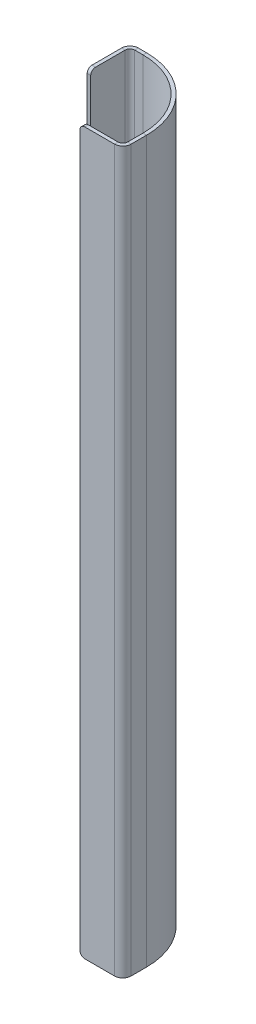
SolidWorks part; units mm, degrees
note: The reader was unsure of these and kept them because the rebuilt part matched: flange length of "Ребро-кромка4", "Ребро-кромка9", "Ребро-кромка10".
ref_plane "Спереди" through (0, 0, 0) normal (0, 0, 1) x (1, 0, 0)
ref_plane "Сверху" through (0, 0, 0) normal (0, 1, 0) x (1, 0, 0)
ref_plane "Справа" through (0, 0, 0) normal (1, 0, 0) x (0, 0, -1)
sketch "Эскиз8" plane through (0, 0, 0) normal (0, 0, 1) x (1, 0, 0)
  line L1 (0, 0) -> (3.5, 0)
  line L2 (0, 0) -> (0, 303)
  line L3 (0, 303) -> (3.5, 303)
  line L4 (3.5, 0) -> (3.5, 303)
  dimension "D1" = 303
  dimension "D2" = 3.5
base flange "Базовая кромка3" sketch "Эскиз8" thickness 1.5 reverse thickness direction no parameters "D1"=2
edge flange "Ребро-кромка4" sketch "Эскиз34" flange angle 90 flange length 35 flange position bend outside bend radius 28.5 thickness 1.5 relief rectangular parameters "D6"=10
sketch "Эскиз34" plane through (3.5, 0, 0) normal (-1, 0, 0) x (0, -1, 0)
  line L2 (-303, 0) -> (-303, 35)
  line L3 (-303, 35) -> (0, 35)
  line L4 (0, 35) -> (0, 0)
  line L9 (0, 0) -> (-303, 0) construction
  line L10 (0, 0) -> (-303, 0)
bend "EdgeBend4" bend radius 28.5 bend angle 90 parameters "D5"=1
edge flange "Ребро-кромка9" sketch "Эскиз47" flange angle 90 flange length 18 flange position bend outside bend radius 2 thickness 1.5 relief rectangular parameters "D6"=10
sketch "Эскиз47" plane through (0, 0, 0) normal (-1, 0, 0) x (0, -1, 0)
  line L0 (-303, 0) -> (0, 0) construction
  line L1 (-303, 0) -> (0, 0)
  line L2 (-303, 0) -> (-303, 16.5)
  line L3 (-303, 16.5) -> (0, 16.5)
  line L4 (0, 16.5) -> (0, 0)
bend "EdgeBend9" bend radius 2 bend angle 90 parameters "D5"=2
edge flange "Ребро-кромка10" sketch "Эскиз50" flange angle 90 flange length 18 flange position bend outside bend radius 2 thickness 1.5 relief rectangular parameters "D6"=10
sketch "Эскиз50" plane through (32, 0, 35) normal (0, 0, 1) x (0, 1, 0)
  line L2 (0, 0) -> (0, 16.5)
  line L3 (0, 16.5) -> (303, 16.5)
  line L4 (303, 16.5) -> (303, 0)
  line L7 (0, 0) -> (303, 0) construction
  line L8 (0, 0) -> (303, 0)
bend "EdgeBend10" bend radius 2 bend angle 90 parameters "D5"=3
fillet "Скругление1" radius 2 4 edges at (15.5, 303, 37.75) (-2.75, 303, 16.5) (-2.75, 0, 16.5) (15.5, 0, 37.75)
sketch "Эскиз51" plane through (-3.5, 0, 0) normal (-1, 0, 0) x (0, 0, 1)
  circle A0 centre (9.25, 286) radius 1.25
  circle A1 centre (9.25, 10) radius 1.25
  point P8 (10.6449, 9.9242)
  dimension "D1" = 2.5
  dimension "D2" = 0
  dimension "D3" = 0
  dimension "D4" = 0
sketch "Сгиб-Линии5" [suppressed] plane through (0, 0, 0) normal (0, 1, 0) x (1, 0, 0)
sketch "Граничная рамка5" [suppressed] plane through (0, 0, 0) normal (0, 1, 0) x (1, 0, 0)
sheet metal parameters "Листовой металл8" thickness 1.5 parameters "D1"=2
flat pattern "Развертка8" [suppressed]
sketch "Сгиб-Линии6" plane through (0, 0, 0) normal (0, 1, 0) x (1, 0, 0)
sketch3d "Граничная рамка6" [suppressed]
  line L0 (-10, 300, 0) -> (-10, 0, 0) construction
  line L1 (0, 300, 0) -> (0, 0, 0) construction
  line L2 (-10, 300, 0) -> (0, 300, 0) construction
  line L3 (-10, 0, 0) -> (0, 0, 0) construction
sheet metal parameters "Листовой металл9" thickness 1.5 parameters "D1"=2
flat pattern "Развертка8"
sketch "Сгиб-Линии6" plane through (0, 0, 0) normal (0, 0, 1) x (1, 0, 0)
  line L0 (27.3565, 0) -> (27.3565, 300) construction
  line L1 (27.3565, 0) -> (27.3565, 300) construction
sketch3d "Граничная рамка6" [suppressed]
  line L0 (54.7129, 300, 0) -> (54.7129, 0, 0) construction
  line L1 (0, 300, 0) -> (0, 0, 0) construction
  line L2 (54.7129, 300, 0) -> (0, 300, 0) construction
  line L3 (54.7129, 0, 0) -> (0, 0, 0) construction
bend of the flat pattern "Плоское состояние-<EdgeBend4>1"
sheet metal parameters "Листовой металл12" thickness 1.5 parameters "D1"=2
flat pattern "Развертка8"
sketch "Сгиб-Линии6" plane through (0, 0, 0) normal (0, 0, 1) x (1, 0, 0)
  line L0 (27.3565, 0) -> (27.3565, 300) construction
  line L1 (27.3565, 0) -> (27.3565, 300) construction
  line L2 (0.1347, 300) -> (0.1347, 0) construction
  line L3 (0.1347, 300) -> (0.1347, 0) construction
sketch3d "Граничная рамка6" [suppressed]
  line L0 (54.7129, 300, 0) -> (54.7129, 0, 0) construction
  line L1 (-16.2306, 300, 0) -> (-16.2306, 0, 0) construction
  line L2 (54.7129, 300, 0) -> (-16.2306, 300, 0) construction
  line L3 (54.7129, 0, 0) -> (-16.2306, 0, 0) construction
bend of the flat pattern "Плоское состояние-<EdgeBend4>1"
bend of the flat pattern "Плоское состояние-<EdgeBend9>1"
sheet metal parameters "Листовой металл13" thickness 1.5 parameters "D1"=2
flat pattern "Развертка8" [suppressed]
sketch "Сгиб-Линии6" plane through (0, 0, 0) normal (0, 0, 1) x (1, 0, 0)
  line L0 (26.1784, 0) -> (26.1784, 303) construction
  line L1 (26.1784, 0) -> (26.1784, 303) construction
  line L2 (-1.8653, 303) -> (-1.8653, 0) construction
  line L3 (-1.8653, 303) -> (-1.8653, 0) construction
  line L4 (57.2221, 0) -> (57.2221, 303) construction
  line L5 (57.2221, 0) -> (57.2221, 303) construction
sketch3d "Граничная рамка6" [suppressed]
  line L0 (73.5872, 0, 0) -> (73.5874, 303, 0) construction
  line L1 (-18.2306, 0, 0) -> (-18.2305, 303, 0) construction
  line L2 (73.5872, 0, 0) -> (-18.2306, 0, 0) construction
  line L3 (73.5874, 303, 0) -> (-18.2305, 303, 0) construction
bend of the flat pattern "Плоское состояние-<EdgeBend4>1"
bend of the flat pattern "Плоское состояние-<EdgeBend9>1"
bend of the flat pattern "Плоское состояние-<EdgeBend10>1"
sketch "Эскиз51-1" [suppressed] plane through (-1.7306, 0, -1.5) normal (0, 0, -1) x (-1, 0, 0)
  circle A0 centre (9.25, 286) radius 1.25
  circle A1 centre (9.25, 10) radius 1.25
  dimension "D1" = 2.5
  dimension "D2" = 165.6331
  dimension "D3" = 236
  dimension "D4" = 285.5352
